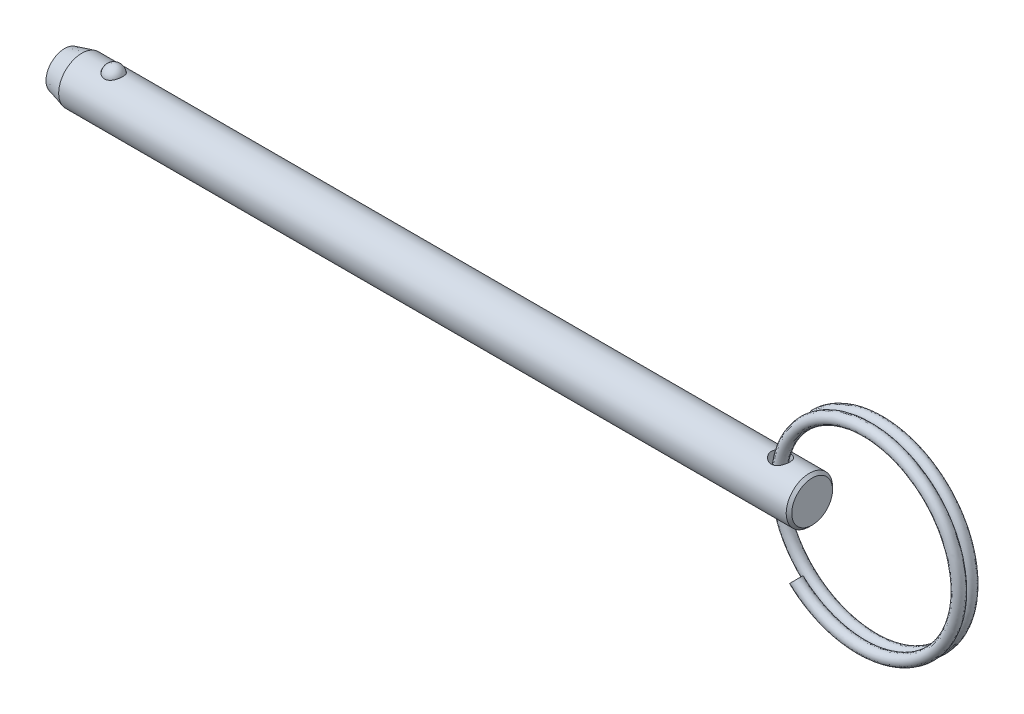
SolidWorks part; units mm, degrees
material "AISI 304"
ref_plane "Front" through (0, 0, 0) normal (0, 0, 1) x (1, 0, 0)
ref_plane "Top" through (0, 0, 0) normal (0, 1, 0) x (1, 0, 0)
ref_plane "Right" through (0, 0, 0) normal (1, 0, 0) x (0, 0, -1)
sketch "Sketch1" plane through (0, 0, 0) normal (0, 0, 1) x (1, 0, 0)
  line L0 (5.588, 2.794) -> (5.207, 3.175)
  line L1 (5.207, 3.175) -> (5.588, 3.175) construction
  line L4 (5.588, 2.794) -> (5.588, 0)
  line L5 (5.588, 3.175) -> (5.588, 2.794) construction
  line L16 (5.207, 3.175) -> (-94.4549, 3.175)
  line L17 (-96.8248, 3.175) -> (-96.8248, 2.54) construction
  line L19 (-94.4549, 3.175) -> (-96.8248, 3.175) construction
  line L22 (-96.8248, -3.175) -> (-94.4549, -3.175) construction
  line L23 (-90.0903, 2.8575) -> (-90.0903, -2.8575) construction
  line L24 (-96.8248, 0) -> (5.588, 0)
  line L27 (5.588, 0) -> (8.382, 0) construction
  line L29 (-96.8248, 0) -> (-96.8248, -2.54) construction
  line L36 (0, 0) -> (0, 3.175) construction
  line L37 (-96.8248, 2.54) -> (-96.8248, 0)
  line L38 (-94.4549, -3.175) -> (5.588, -3.175) construction
  line L39 (-96.8248, -2.54) -> (-96.8248, -3.175) construction
  line L40 (-94.4549, 3.175) -> (-96.8248, 2.54)
  line L42 (-94.4549, -3.175) -> (-96.8248, -2.54) construction
  line L43 (-94.4549, 3.175) -> (-94.4549, -3.175) construction
  circle A2 centre (-90.0903, 2.8575) radius 1.2319 construction
  point P35 (-88.9, 3.175)
  dimension "D2" = 5.715
  dimension "D11" = 0.9144
  dimension "A" = 6.35
  dimension "D" = 5.588
  dimension "E" = 7.2644
  dimension "D3" = 0.381
  dimension "Useable Length" = 88.9
  dimension "D12" = 5.08
  dimension "C" = 7.9248
  dimension "A1" = 15
revolve "Revolve1" add sketch "Sketch1" angle 360 about L27
sketch "Sketch2" plane through (0, 0, 0) normal (0, 0, 1) x (1, 0, 0)
  line L0 (-88.833, 2.8575) -> (-91.3476, 2.8575)
  line L1 (-90.0903, 4.0894) -> (-90.0903, 4.1148) construction
  line L2 (-88.833, 2.8575) -> (-86.3184, 2.8575) construction
  circle A0 centre (-90.0903, 2.8575) radius 1.2319 construction
  circle A1 centre (-90.0903, 2.8575) radius 1.2319 construction
  arc A2 (-91.3476, 2.8575) -> (-88.833, 2.8575) centre (-90.0903, 2.8575) cw
  dimension "D1" = 0.0254
revolve "Cut-Revolve1" cut sketch "Sketch2" angle 360 about L2
sketch "Sketch3" plane through (0, 0, 0) normal (0, 0, 1) x (1, 0, 0)
  line L0 (-88.8584, 2.8575) -> (-91.3222, 2.8575)
  line L1 (-88.8584, 2.8575) -> (-86.3946, 2.8575) construction
  circle A0 centre (-90.0903, 2.8575) radius 1.2319 construction
  arc A1 (-88.8584, 2.8575) -> (-91.3222, 2.8575) centre (-90.0903, 2.8575) ccw
revolve "Revolve2" add sketch "Sketch3" angle 360 about L1
sketch "Sketch4" plane through (0, 0, 0) normal (0, 0, 1) x (1, 0, 0)
  line L1 (1.27, -3.175) -> (2.54, -3.175)
  line L2 (1.27, -3.175) -> (1.27, 3.175)
  line L3 (1.27, 3.175) -> (2.54, 3.175)
  line L4 (2.54, -3.175) -> (2.54, 3.175)
  line L5 (1.27, -3.175) -> (1.27, -4.445) construction
  line L6 (2.54, 3.175) -> (5.588, 3.175) construction
  line L8 (0, -3.175) -> (0, 3.175) construction
  line L9 (0, 0) -> (1.27, 0) construction
  line L11 (1.27, 0) -> (2.54, 0) construction
  line L12 (5.207, 3.175) -> (-94.4549, 3.175) construction
  line L14 (-94.4549, -3.175) -> (5.588, -3.175) construction
  dimension "D1" = 2.54
revolve "Cut-Revolve2" cut sketch "Sketch4" angle 360 about L2
sketch "Sketch5" plane through (0, 0, 0) normal (0, 0, 1) x (1, 0, 0)
  line L0 (0, 0) -> (0.293, 0) construction
  line L1 (0.293, 0) -> (0.293, 3.175) construction
  line L2 (5.207, 3.175) -> (-94.4549, 3.175) construction
  line L3 (13.755, 0) -> (27.217, 0) construction
  line L4 (2.54, 3.175) -> (2.247, 3.175) construction
  line L5 (1.27, 3.175) -> (2.54, 3.175) construction
  line L6 (0.6728, 3.175) -> (0.6728, -3.175) construction
  line L7 (0.293, 3.175) -> (0, 3.175) construction
  line L8 (1.27, -3.175) -> (2.54, -3.175) construction
  line L9 (0.6728, -3.175) -> (2.54, -3.175) construction
  line L10 (0.293, 0) -> (13.755, 0) construction
  line L11 (13.755, 0) -> (8.7098, -10.8195) construction
  line L12 (2.247, 3.175) -> (0.6728, 3.175) construction
  line L13 (13.755, 11.938) -> (13.755, 13.462) construction
  line L14 (8.7098, -10.8195) -> (8.3878, -11.5101) construction
  circle A0 centre (13.755, 0) radius 13.462
  circle A1 centre (13.755, 0) radius 11.938 construction
  circle A2 centre (13.755, 0) radius 12.7 construction
  point P26 (13.755, 12.7)
  dimension "D1" = 65
  dimension "R Ring Dia" = 25.4
  dimension "Ring OD" = 1.524
curve "Helix/Spiral1" pitch 1.5494 height 1.3557 radius 13.462 left hand yes centre (13.755, 0, 0) axis (0, 0, -1) start towards (1, 0, 0)
sketch "Sketch6" plane through (114.0038, 0, 0) normal (0, 1, 0) x (0, 0, -1)
  line L0 (0, 112.1868) -> (0, 112.9488) construction
  line L1 (0, 112.9488) -> (0, 113.7108) construction
  circle A0 centre (0, 112.9488) radius 0.762
  dimension "D1" = 1.524
sketch "Sketch7" plane through (0, 0, 0) normal (0, 0, 1) x (1, 0, 0)
  circle A0 centre (13.755, 0) radius 13.462 construction
  circle A1 centre (13.755, 0) radius 13.462
curve "Helix/Spiral2" pitch 1.5494 height 1.3557 radius 13.462 left hand yes centre (13.755, 0, 0) axis (0, 0, 1) start towards (1, 0, 0)
sweep "Sweep1" add profiles "Sketch6" path "Helix/Spiral1"
sweep "Sweep2" add profiles "Sketch6<2>" path "Helix/Spiral2"
sketch "Sketch6<2>" plane through (114.0038, 0, 0) normal (0, 1, 0) x (0, 0, -1) same geometry as "Sketch6"
ref_plane "Plane1" through (0, -10.8195, 0) normal (0, 1, 0) x (-1, 0, 0)
sketch "Sketch8" plane through (0, -10.8195, 0) normal (0, 1, 0) x (-1, 0, 0)
  line L0 (296.0902, 0) -> (-8.7098, 0) construction
  line L1 (10.3402, -0.7779) -> (4.5066, -0.7779)
  line L2 (3.5004, -0.9415) -> (-7.2005, -4.517)
  line L3 (-7.2005, 4.517) -> (3.5004, 0.9415)
  line L4 (4.5066, 0.7779) -> (282.8738, 0.7779)
  line L5 (283.88, 0.9415) -> (294.5809, 4.517)
  line L6 (277.0402, -0.7779) -> (282.8738, -0.7779)
  line L7 (283.88, -0.9415) -> (294.5809, -4.517)
  line L8 (10.3402, -0.7779) -> (10.3402, 0.7779) construction
  arc A0 (-7.2005, 4.517) -> (-7.2005, -4.517) centre (-8.7098, 0) ccw
  arc A1 (294.5809, -4.517) -> (294.5809, 4.517) centre (296.0902, 0) ccw
  arc A2 (4.5066, -0.7779) -> (3.5004, -0.9415) centre (4.5066, -3.9529) ccw
  arc A3 (3.5004, 0.9415) -> (4.5066, 0.7779) centre (4.5066, 3.9529) ccw
  arc A4 (282.8738, -0.7779) -> (283.88, -0.9415) centre (282.8738, -3.9529) cw
  arc A5 (282.8738, 0.7779) -> (283.88, 0.9415) centre (282.8738, 3.9529) ccw
  point P6 (10.3402, 0)
  point P16 (3.9902, -0.7779)
  point P20 (3.9902, 0.7779)
  point P23 (283.3902, -0.7779)
  point P26 (283.3902, 0.7779)
  dimension "D2" = 4.7625
  dimension "D3" = 1.5557
  dimension "D6" = 3.175
  dimension "Lanyard Length" = 304.8
  dimension "D4" = 6.35
  dimension "D5" = 12.7
ref_plane "Plane2" through (-10.3402, 0, 0) normal (1, 0, 0) x (0, 0, -1)
sketch "Sketch9" plane through (-10.3402, 0, 0) normal (1, 0, 0) x (0, 0, -1)
  circle A0 centre (0.7779, -10.8195) radius 0.7779
sweep "Sweep3" [suppressed] add profiles "Sketch9" path "Sketch8"
sketch "Sketch10" [suppressed] plane through (-10.3402, 0, 0) normal (1, 0, 0) x (0, 0, -1)
  arc A0 (-0.3849, -10.1482) -> (-0.3849, -11.4908) centre (-0.7779, -10.8195) ccw
  circle A1 centre (0.7779, -10.8195) radius 0.7779
  arc A2 (0.3849, -11.4908) -> (0.3849, -10.1482) centre (0.7779, -10.8195) ccw
  arc A3 (-0.3849, -11.4908) -> (0.3849, -11.4908) centre (0, -12.1485) cw
  arc A4 (-0.3869, -9.3301) -> (-0.3869, -12.3089) centre (-0.7779, -10.8195) ccw
  arc A5 (0.3869, -12.3089) -> (0.3869, -9.3301) centre (0.7779, -10.8195) ccw
  circle A6 centre (-0.7779, -10.8195) radius 1.5399 construction
  circle A7 centre (-0.7779, -10.8195) radius 0.7779 construction
  arc A8 (-0.3849, -10.1482) -> (0.3849, -10.1482) centre (0, -9.4905) ccw
  arc A9 (-0.3869, -9.3301) -> (0.3869, -9.3301) centre (0, -7.856) ccw
  arc A10 (0.3869, -12.3089) -> (-0.3869, -12.3089) centre (0, -13.783) ccw
  point P4 (-0.034, -10.2746)
  point P8 (2.3178, -10.502)
  point P9 (0.762, -10.502)
  dimension "D3" = 1.524
  dimension "D4" = 0.762
  dimension "D2" = 0.762
  dimension "D1" = 0
extrude "Extrude1" [suppressed] add sketch "Sketch10" along normal blind 5.715 separate body
sketch "Sketch11" [suppressed] plane through (-277.0402, 0, 0) normal (1, 0, 0) x (0, 0, -1)
  arc A4 (-0.3849, -10.1482) -> (-0.3849, -11.4908) centre (-0.7779, -10.8195) ccw
  arc A5 (0.3849, -11.4908) -> (-0.3849, -11.4908) centre (0, -12.1485) ccw
  arc A6 (0.3849, -11.4908) -> (0.3849, -10.1482) centre (0.7779, -10.8195) ccw
  arc A7 (-0.3849, -10.1482) -> (0.3849, -10.1482) centre (0, -9.4905) ccw
  arc A8 (-0.3849, -10.1482) -> (-0.3849, -11.4908) centre (-0.7779, -10.8195) ccw
  arc A9 (0.3849, -11.4908) -> (-0.3849, -11.4908) centre (0, -12.1485) ccw
  arc A10 (0.3849, -11.4908) -> (0.3849, -10.1482) centre (0.7779, -10.8195) ccw
  arc A11 (-0.3849, -10.1482) -> (0.3849, -10.1482) centre (0, -9.4905) ccw
  arc A12 (-0.3869, -9.3301) -> (-0.3869, -12.3089) centre (-0.7779, -10.8195) ccw
  arc A13 (0.3869, -12.3089) -> (-0.3869, -12.3089) centre (0, -13.783) ccw
  arc A14 (0.3869, -12.3089) -> (0.3869, -9.3301) centre (0.7779, -10.8195) ccw
  arc A15 (-0.3869, -9.3301) -> (0.3869, -9.3301) centre (0, -7.856) ccw
  arc A16 (-0.3869, -9.3301) -> (-0.3869, -12.3089) centre (-0.7779, -10.8195) ccw
  arc A17 (0.3869, -12.3089) -> (-0.3869, -12.3089) centre (0, -13.783) ccw
  arc A18 (0.3869, -12.3089) -> (0.3869, -9.3301) centre (0.7779, -10.8195) ccw
  arc A19 (-0.3869, -9.3301) -> (0.3869, -9.3301) centre (0, -7.856) ccw
  dimension "D1" = 0
  dimension "D2" = 0
extrude "Extrude2" [suppressed] add sketch "Sketch11" against normal blind 5.715 separate body
sketch "Sketch12" plane through (0, -10.8195, 0) normal (0, 1, 0) x (-1, 0, 0)
  line L0 (326.8712, -5.2864) -> (321.3086, -5.2864) construction
  line L1 (326.8712, -5.9214) -> (310.5026, -5.9214)
  line L2 (326.8712, -5.9214) -> (326.8712, -4.6514)
  line L3 (326.8712, -4.6514) -> (310.7265, -4.6514)
  line L4 (310.5026, -5.9214) -> (310.7265, -4.6514) construction
  line L5 (310.5026, -5.9214) -> (295.1212, -0.3231)
  line L6 (321.3086, -5.2864) -> (310.6146, -5.2864) construction
  line L7 (310.7265, -4.6514) -> (295.5555, 0.8704)
  line L8 (295.1212, -0.3231) -> (295.5555, 0.8704)
  line L9 (310.6146, -5.2864) -> (300.5655, -1.6289) construction
  line L10 (300.5655, -1.6289) -> (295.3383, 0.2737) construction
  arc A0 (294.5809, -4.517) -> (294.5809, 4.517) centre (296.0902, 0) ccw construction
  dimension "D1" = 20
  dimension "D2" = 31.75
  dimension "D3" = 1.27
  dimension "D4" = 5.5626
extrude "Extrude3" [suppressed] add sketch "Sketch12" along normal mid plane 12.7 separate body
sketch "Sketch13" [suppressed] plane through (0, 0, -4.6514) normal (0, 0, 1) x (1, 0, 0)
  line L0 (-326.8712, -10.8195) -> (-310.7265, -10.8195) construction
  line L1 (-324.8782, -4.4695) -> (-326.8712, -4.4695)
  line L2 (-326.8712, -4.4695) -> (-310.7265, -4.4695) construction
  line L3 (-326.8712, -4.4695) -> (-328.8642, -4.4695)
  line L4 (-328.8642, -4.4695) -> (-328.8642, -17.1695)
  line L5 (-328.8642, -17.1695) -> (-326.8712, -17.1695)
  line L6 (-326.8712, -17.1695) -> (-324.8782, -17.1695)
  line L7 (-326.8712, -17.1695) -> (-310.7265, -17.1695) construction
  arc A0 (-324.8782, -4.4695) -> (-324.8782, -17.1695) centre (-315.7587, -10.8195) ccw
  circle A1 centre (-321.3086, -10.8195) radius 2.5781
  dimension "D1" = 5.1562
  dimension "D2" = 11.1125
extrude "Extrude4" [suppressed] cut sketch "Sketch13" against normal up to surface (1.27 mm away)
sketch "Sketch14" [suppressed] plane through (-34.8532, 0, 95.7583) normal (-0.342, 0, 0.9397) x (0.9397, 0, 0.342)
  line L3 (-279.4267, -4.4695) -> (-277.4337, -4.4695)
  line L4 (-277.4337, -4.4695) -> (-275.4407, -4.4695)
  line L5 (-275.4407, -4.4695) -> (-275.4407, -17.1695)
  line L6 (-275.4407, -17.1695) -> (-277.4337, -17.1695)
  line L7 (-277.4337, -17.1695) -> (-279.4267, -17.1695)
  line L8 (-277.4337, -4.4695) -> (-277.4337, -17.1695) construction
  line L9 (-293.5783, -4.4695) -> (-277.4337, -4.4695) construction
  line L10 (-293.6903, -10.8195) -> (-282.9963, -10.8195) construction
  arc A0 (-279.4267, -17.1695) -> (-279.4267, -4.4695) centre (-288.5462, -10.8195) ccw
  circle A1 centre (-282.9963, -10.8195) radius 2.5781
  dimension "D1" = 5.1562
  dimension "D2" = 11.1125
extrude "Extrude6" [suppressed] cut sketch "Sketch14" against normal up to surface (1.27 mm away)
sketch "Sketch15" [suppressed] plane through (0, 0, 0) normal (0, 0, 1) x (1, 0, 0)
  line L1 (-257.8086, -4.4695) -> (-99.0586, -4.4695)
  line L2 (-257.8086, -4.4695) -> (-270.5086, -17.1695)
  line L3 (-270.5086, -17.1695) -> (-111.7586, -17.1695)
  line L4 (-99.0586, -4.4695) -> (-111.7586, -17.1695)
  line L5 (-324.8782, -4.4695) -> (-310.7265, -4.4695) construction
  line L6 (-324.8782, -17.1695) -> (-310.7265, -17.1695) construction
  circle A0 centre (-321.3086, -10.8195) radius 2.5781 construction
  dimension "D1" = 63.5
  dimension "D2" = 158.75
  dimension "D3" = 45
extrude "Extrude7" [suppressed] cut sketch "Sketch15" against normal through all and the other way through all
move or copy body "Body-Move/Copy1" [suppressed] bodies to move or copy 147 151 144 copy no translate (152.4, 0, 0)
sketch "Sketch16" [suppressed] plane through (0, 0, 0) normal (0, 0, 1) x (1, 0, 0)
  line L0 (-111.7586, -6.057) -> (-111.7586, -9.232) construction
  line L1 (-111.7586, -9.232) -> (-109.2186, -8.2795) construction
  line L2 (-109.2186, -8.2795) -> (-114.2986, -13.3595) construction
  line L3 (-114.2986, -13.3595) -> (-111.7586, -12.407) construction
  line L4 (-111.7586, -12.407) -> (-111.7586, -15.582) construction
  line L5 (-112.5364, -11.5974) -> (-110.9807, -10.0416) construction
  line L6 (-105.4086, -15.582) -> (-105.4086, -12.407) construction
  line L7 (-105.4086, -12.407) -> (-107.9486, -13.3595) construction
  line L8 (-107.9486, -13.3595) -> (-102.8686, -8.2795) construction
  line L9 (-102.8686, -8.2795) -> (-105.4086, -9.232) construction
  line L10 (-105.4086, -9.232) -> (-105.4086, -6.057) construction
  line L11 (-104.6307, -10.0416) -> (-106.1864, -11.5974) construction
  line L14 (-4.5066, -10.8195) -> (-282.8738, -10.8195) construction
  dimension "D1" = 3.175
  dimension "D2" = 3.175
  dimension "D3" = 5.08
  dimension "D4" = 1.5875
equation "\"D12@Sketch1\"=\"A@Sketch1\" * 0.80"
equation "\"D2@Sketch1\"=\"A@Sketch1\" * 0.9"
equation "\"D1@Sketch4\" = \"A@Sketch1\" / 2.5"
equation "\"Ring OD@Sketch5\" = \"R Ring Dia@Sketch5\" * 0.06"
equation "\"D4@Helix/Spiral1\"=\"Ring OD@Sketch5\" + 0.001"
equation "\"D1@Sketch6\"=\"Ring OD@Sketch5\""
equation "\"D4@Helix/Spiral2\" = \"D4@Helix/Spiral1\""
equation "\"D5@Helix/Spiral2\" = \"D5@Helix/Spiral1\""
equation "\"D1@Sketch14\" = \"D1@Sketch13\""
equation "\"D2@Sketch14\" = \"D2@Sketch13\""
